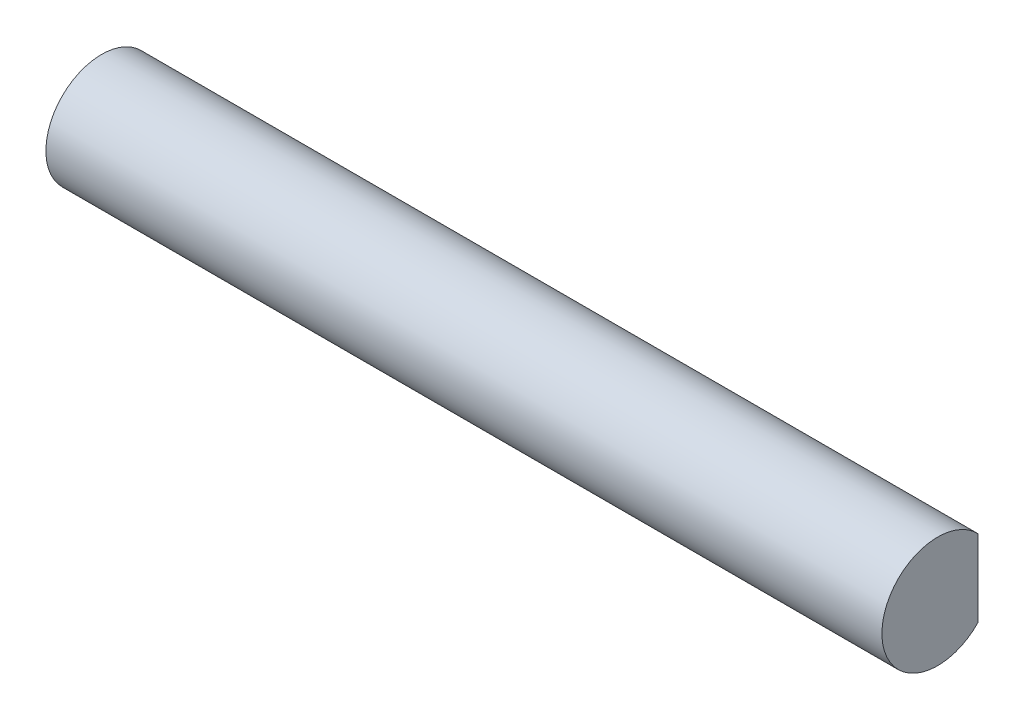
SolidWorks part; units mm, degrees
ref_plane "Front Plane" through (0, 0, 0) normal (0, 0, 1) x (1, 0, 0)
ref_plane "Top Plane" through (0, 0, 0) normal (0, 1, 0) x (1, 0, 0)
ref_plane "Right Plane" through (0, 0, 0) normal (1, 0, 0) x (0, 0, -1)
sketch "Sketch5" plane through (0, 0, 3.7) normal (1, 0, 0) x (0, 1, 0)
  line L0 (0, -16.5814) -> (0, 9.1814) construction
  line L5 (-7.5, -2.6947) -> (-6.4, -4.6) construction
  line L6 (7.5, -2.6947) -> (6.4, -4.6) construction
  line L7 (5.3668, 1) -> (7.5, -2.6947) construction
  line L8 (-5.3668, 1) -> (5.3668, 1) construction
  line L9 (-5.3668, 1) -> (-7.5, -2.6947) construction
  line L10 (7.7309, -2.6947) -> (6.5732, -4.7)
  line L11 (5.4823, 1.2) -> (7.7309, -2.6947)
  line L12 (-5.4823, 1.2) -> (5.4823, 1.2)
  line L13 (-5.4823, 1.2) -> (-7.7309, -2.6947)
  line L14 (-7.7309, -2.6947) -> (-6.5732, -4.7)
  line L15 (-6.5732, -4.7) -> (6.5732, -4.7)
  line L17 (0, -9.7207) -> (0, 9.7207) construction
  line L18 (-6.9, -10.9381) -> (6.9, -10.9381)
  line L19 (0, -10.9381) -> (0, -3.7) construction
  circle A0 centre (0, -3.7) radius 10 construction
  arc A1 (-6.9, -10.9381) -> (6.9, -10.9381) centre (0, -3.7) cw
  point P18 (0, -13.7)
sketch "Sketch8" plane through (0, 0, 3.7) normal (0, -1, 0) x (1, 0, 0)
  line L2 (0, -9.7207) -> (-145, -9.7207)
  line L3 (0, -9.9381) -> (-145, -9.9381)
  line L4 (0, -10.9381) -> (-150, -10.9381)
  point P0 (0, -9.7207)
  point P1 (0.0193, -10.0619)
  point P3 (0, -10.9381)
  point P4 (0, -10.1696)
  point P5 (0, 0)
  point P6 (0, -10.079)
  point P15 (-145, -9.9886)
  point P16 (0, -10.2652)
  point P19 (0, -10)
sketch "Sketch9" plane through (0, 0, 3.7) normal (1, 0, 0) x (0, 1, 0)
  line L0 (-6.9, -10.9381) -> (6.9, -10.9381) construction
  line L3 (-6.9, -10.9381) -> (6.9, -10.9381) construction
  line L4 (-6.4874, -9.9381) -> (6.4874, -9.9381)
  line L5 (-6.4017, -9.7381) -> (6.4017, -9.7381)
  arc A3 (6.9, -10.9381) -> (-6.9, -10.9381) centre (0, -3.7) ccw construction
  arc A4 (6.4874, -9.9381) -> (-6.4874, -9.9381) centre (0, -3.7) ccw
  arc A5 (6.4017, -9.7381) -> (-6.4017, -9.7381) centre (0, -3.7) ccw
sketch "Sketch1" plane through (0, 0, 0) normal (1, 0, 0) x (0, 0, -1)
  line L37 (7.2381, -6.9) -> (7.2381, 6.9) construction
  line L39 (7.2381, -6.9) -> (7.2381, 6.9)
  line L42 (1, 6.5732) -> (-1.0053, 7.7309)
  line L43 (1, -6.5732) -> (1, 6.5732)
  line L44 (-1.0053, -7.7309) -> (1, -6.5732)
  line L45 (-4.9, -5.4823) -> (-1.0053, -7.7309)
  line L46 (-4.9, 5.4823) -> (-4.9, -5.4823)
  line L47 (-1.0053, 7.7309) -> (-4.9, 5.4823)
  line L48 (1, 6.5732) -> (-1.0053, 7.7309)
  line L49 (1, -6.5732) -> (1, 6.5732)
  line L50 (-1.0053, -7.7309) -> (1, -6.5732)
  line L51 (-4.9, -5.4823) -> (-1.0053, -7.7309)
  line L52 (-4.9, 5.4823) -> (-4.9, -5.4823)
  line L53 (-1.0053, 7.7309) -> (-4.9, 5.4823)
  arc A5 (7.2381, 6.9) -> (7.2381, -6.9) centre (0, 0) ccw construction
  arc A6 (7.2381, 6.9) -> (7.2381, -6.9) centre (0, 0) ccw
  dimension "D2" = 0
extrude "Bar" add sketch "Sketch1" against normal up to vertex (150 mm away) up to point (-150, 0, -7.2381)
sketch "Sketch10" plane through (-150, 0, 0) normal (-1, 0, 0) x (0, 0, 1)
  line L0 (-6.2381, -6.4874) -> (-6.2381, 6.4874) construction
  line L1 (-6.2381, -6.4874) -> (-6.2381, 6.4874)
  arc A0 (-6.2381, -6.4874) -> (-6.2381, 6.4874) centre (0, 0) ccw construction
  arc A1 (-6.2381, -6.4874) -> (-6.2381, 6.4874) centre (0, 0) ccw
extrude "Cut-Extrude4" cut sketch "Sketch10" against normal up to vertex (5 mm away) up to point (-145, 0, -6.2381)
sketch "Sketch6"
  line L12 (0, 0) -> (-150, 0) construction
  line L13 (-0.8, 6.1) -> (-49.7333, 6.1)
  line L14 (-0.8, 6.1) -> (-0.8, -6.1)
  line L15 (-0.8, -6.1) -> (-49.7333, -6.1)
  line L24 (0, -6.9) -> (0, 6.9)
  line L25 (0, 6.9) -> (-150, 6.9)
  line L26 (-150, 6.9) -> (-150, -6.9)
  line L27 (-150, -6.9) -> (0, -6.9)
  line L28 (0, -6.9) -> (0, 6.9) construction
  line L29 (0, 6.9) -> (-150, 6.9) construction
  line L30 (-150, 6.9) -> (-150, -6.9) construction
  line L31 (-150, -6.9) -> (0, -6.9) construction
  line L32 (-49.7333, 6.1) -> (-49.7333, -6.1)
  line L33 (-50.5333, 6.1) -> (-50.5333, -6.1)
  line L34 (-50.5333, 6.1) -> (-99.4667, 6.1)
  line L35 (-99.4667, 6.1) -> (-99.4667, -6.1)
  line L36 (-50.5333, -6.1) -> (-99.4667, -6.1)
  line L37 (-100.2667, 6.1) -> (-100.2667, -6.1)
  line L38 (-100.2667, 6.1) -> (-149.2, 6.1)
  line L39 (-149.2, 6.1) -> (-149.2, -6.1)
  line L40 (-100.2667, -6.1) -> (-149.2, -6.1)
  dimension "D2" = 0.8
  dimension "D3" = 0.8
  dimension "D5" = 0.8
  dimension "D6" = 0.8
  dimension "D1" = 0
  dimension "D4" = 3
extrude "Cut-Extrude3" cut sketch "Sketch6" against normal up to next
sketch "Sketch11" plane through (0, 0, 0) normal (1, 0, 0) x (0, 0, -1)
  line L1 (7.2381, -6.9) -> (7.2381, 6.9)
  line L2 (7.2381, -6.9) -> (7.2381, 6.9)
  arc A1 (7.2381, 6.9) -> (7.2381, -6.9) centre (0, 0) ccw
  arc A2 (7.2381, 6.9) -> (7.2381, -6.9) centre (0, 0) ccw
  dimension "D1" = 0
extrude "Boss-Extrude2" add sketch "Sketch11" against normal blind 0.8
